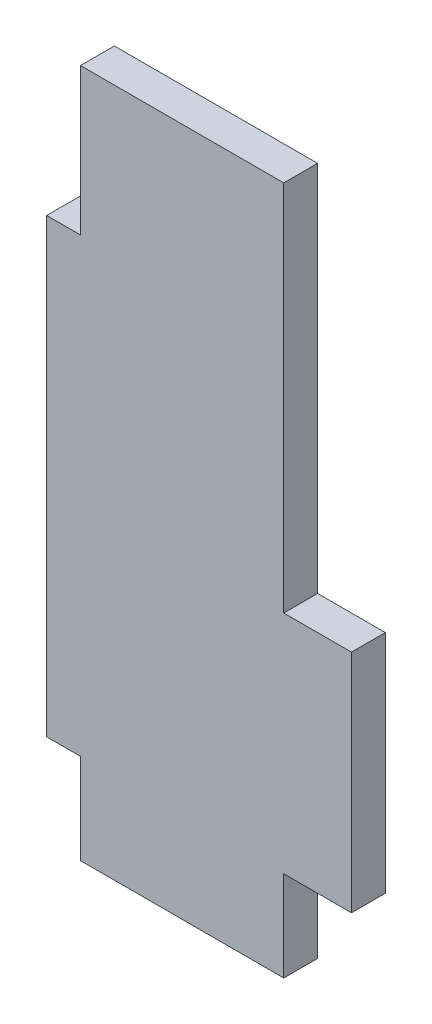
SolidWorks part; units mm, degrees
ref_plane "Front Plane" through (0, 0, 0) normal (0, 0, 1) x (1, 0, 0)
ref_plane "Top Plane" through (0, 0, 0) normal (0, 1, 0) x (1, 0, 0)
ref_plane "Right Plane" through (0, 0, 0) normal (1, 0, 0) x (0, 0, -1)
sketch "Sketch1" plane through (0, 0, 0) normal (0, 0, 1) x (1, 0, 0)
  line L1 (-18, 61) -> (0, 61)
  line L2 (-18, 61) -> (-18, 0)
  line L3 (-18, 0) -> (0, 0)
  line L4 (0, 61) -> (0, 0)
  dimension "D1" = 61
  dimension "D2" = 18
extrude "Base Shape" add sketch "Sketch1" along normal blind 3
sketch "Sketch2" plane through (0, 0, 3) normal (0, 0, 1) x (1, 0, 0)
  line L0 (-18, 61) -> (-18, 0) construction
  line L1 (-18, 8) -> (-21, 8)
  line L2 (-18, 8) -> (-18, 48)
  line L3 (-18, 48) -> (-21, 48)
  line L4 (-21, 8) -> (-21, 48)
  line L5 (0, 0) -> (0, 61) construction
  line L6 (0, 8) -> (6, 8)
  line L7 (0, 8) -> (0, 28)
  line L8 (0, 28) -> (6, 28)
  line L9 (6, 8) -> (6, 28)
  line L10 (-18, 0) -> (0, 0) construction
  line M11 (0, 0) -> (0, 61)
  dimension "D1" = 8
  dimension "D2" = 40
  dimension "D3" = 3
  dimension "D4" = 6
  dimension "D5" = 20
extrude "Boss-Extrude2" add sketch "Sketch2" against normal up to surface (3 mm away) contours L6 L9 L8 M11 | L4 L3 L2 L1 region at (3, 18, 3) up to face at (-9, 30.5, 0)
